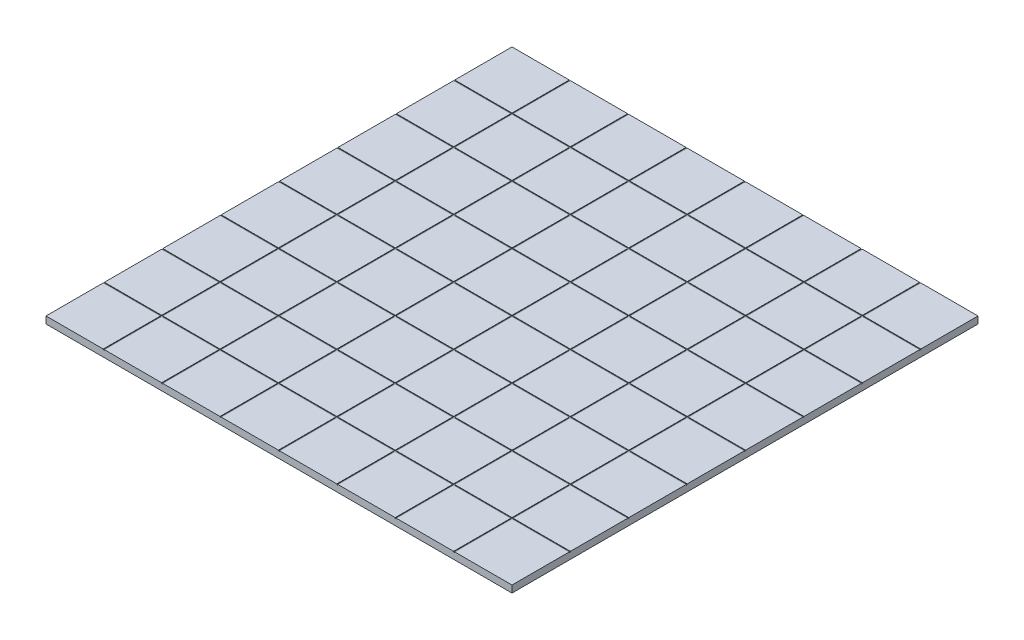
SolidWorks part; units mm, degrees
ref_plane "Front Plane" through (0, 0, 0) normal (0, 0, 1) x (1, 0, 0)
ref_plane "Top Plane" through (0, 0, 0) normal (0, 1, 0) x (1, 0, 0)
ref_plane "Right Plane" through (0, 0, 0) normal (1, 0, 0) x (0, 0, -1)
sketch "Sketch1" plane through (0, 0, 0) normal (0, 1, 0) x (1, 0, 0)
  line L1 (0, 0) -> (200, 0)
  line L2 (0, 0) -> (0, 200)
  line L3 (0, 200) -> (200, 200)
  line L4 (200, 0) -> (200, 200)
  dimension "D1" = 200
  dimension "D2" = 200
extrude "Boss-Extrude1" add sketch "Sketch1" along normal blind 3
sketch "Sketch2" plane through (0, 3, 0) normal (0, 1, 0) x (1, 0, 0)
  line L0 (200, 200) -> (0, 200) construction
  line L1 (24.5625, 200) -> (25.0625, 200)
  line L2 (24.5625, 200) -> (24.5625, 0)
  line L3 (24.5625, 0) -> (25.0625, 0)
  line L4 (25.0625, 200) -> (25.0625, 0)
  line L5 (0, 0) -> (200, 0) construction
  line L6 (200, 0) -> (200, 200) construction
  line L7 (49.625, 0) -> (50.125, 0)
  line L8 (49.625, 0) -> (49.625, 200)
  line L9 (49.625, 200) -> (50.125, 200)
  line L10 (50.125, 0) -> (50.125, 200)
  line L11 (99.75, 0) -> (100.25, 0)
  line L12 (99.75, 0) -> (99.75, 200)
  line L13 (99.75, 200) -> (100.25, 200)
  line L14 (100.25, 0) -> (100.25, 200)
  line L15 (74.6875, 0) -> (75.1875, 0)
  line L16 (74.6875, 0) -> (74.6875, 200)
  line L17 (74.6875, 200) -> (75.1875, 200)
  line L18 (75.1875, 0) -> (75.1875, 200)
  line L19 (124.8125, 0) -> (125.3125, 0)
  line L20 (124.8125, 0) -> (124.8125, 200)
  line L21 (124.8125, 200) -> (125.3125, 200)
  line L22 (125.3125, 0) -> (125.3125, 200)
  line L23 (149.875, 0) -> (150.375, 0)
  line L24 (149.875, 0) -> (149.875, 200)
  line L25 (149.875, 200) -> (150.375, 200)
  line L26 (150.375, 0) -> (150.375, 200)
  line L27 (174.9375, 0) -> (175.4375, 0)
  line L28 (174.9375, 0) -> (174.9375, 200)
  line L29 (174.9375, 200) -> (175.4375, 200)
  line L30 (175.4375, 0) -> (175.4375, 200)
  line L31 (0, 200) -> (0, 0) construction
  line L33 (0, 175.4375) -> (200, 175.4375)
  line L34 (0, 175.4375) -> (0, 174.9375)
  line L35 (0, 174.9375) -> (200, 174.9375)
  line L36 (200, 175.4375) -> (200, 174.9375)
  line L37 (0, 150.375) -> (200, 150.375)
  line L38 (0, 150.375) -> (0, 149.875)
  line L39 (0, 149.875) -> (200, 149.875)
  line L40 (200, 150.375) -> (200, 149.875)
  line L41 (0, 125.3125) -> (200, 125.3125)
  line L42 (0, 125.3125) -> (0, 124.8125)
  line L43 (0, 124.8125) -> (200, 124.8125)
  line L44 (200, 125.3125) -> (200, 124.8125)
  line L45 (0, 100.25) -> (200, 100.25)
  line L46 (0, 100.25) -> (0, 99.75)
  line L47 (0, 99.75) -> (200, 99.75)
  line L48 (200, 100.25) -> (200, 99.75)
  line L49 (0, 75.1875) -> (200, 75.1875)
  line L50 (0, 75.1875) -> (0, 74.6875)
  line L51 (0, 74.6875) -> (200, 74.6875)
  line L52 (200, 75.1875) -> (200, 74.6875)
  line L53 (0, 50.125) -> (200, 50.125)
  line L54 (0, 50.125) -> (0, 49.625)
  line L55 (0, 49.625) -> (200, 49.625)
  line L56 (200, 50.125) -> (200, 49.625)
  line L57 (0, 25.0625) -> (200, 25.0625)
  line L58 (0, 25.0625) -> (0, 24.5625)
  line L59 (0, 24.5625) -> (200, 24.5625)
  line L60 (200, 25.0625) -> (200, 24.5625)
  line M29 (0, 200) -> (0, 0)
  dimension "D1" = 0.5
  dimension "D2" = 0.5
  dimension "D3" = 0.5
  dimension "D4" = 0.5
  dimension "D5" = 0.5
  dimension "D6" = 0.5
  dimension "D7" = 0.5
  dimension "D8" = 24.5625
  dimension "D9" = 0.5
  dimension "D10" = 24.5625
  dimension "D11" = 24.5625
  dimension "D12" = 24.5625
  dimension "D13" = 24.5625
  dimension "D14" = 24.5625
  dimension "D15" = 24.5625
  dimension "D16" = 24.5625
  dimension "D17" = 0.5
  dimension "D18" = 24.5625
  dimension "D19" = 0.5
  dimension "D20" = 24.5625
  dimension "D21" = 0.5
  dimension "D22" = 24.5625
  dimension "D23" = 0.5
  dimension "D24" = 24.5625
  dimension "D25" = 0.5
  dimension "D26" = 24.5625
  dimension "D27" = 0.5
  dimension "D28" = 24.5625
  dimension "D29" = 0.5
  dimension "D30" = 24.5625
  dimension "D31" = 24.5625
extrude "Cut-Extrude1" cut sketch "Sketch2" against normal blind 0.25 contours L51 L2 L49 M29 | L2 L3 L4 L1 | L49 L52 L51 L50 | L57 L60 L59 L58 | L55 L56 L53 L54 | L47 L48 L45 L46 | L41 L44 L43 L42 | L39 L40 L37 L38 | L33 L36 L35 L34 | L8 L9 L10 L7 | L18 L17 L16 L15 | L12 L13 L14 L11 | L20 L21 L22 L19 | L26 L25 L24 L23 | L30 L29 L28 L27 region at (12.2813, 3, -74.9375)
sketch "Sketch4" plane through (0, 0, 0) normal (0, -1, 0) x (1, 0, 0)
  line L0 (12.28, -186.22) -> (12.28, -189.22)
  line L1 (10.33, -186.22) -> (14.23, -186.22)
  line L2 (10.33, -186.22) -> (10.33, -189.22)
  line L3 (10.33, -189.22) -> (14.23, -189.22)
  line L4 (24.5625, -175.4375) -> (0, -175.4375)
  line L5 (24.5625, -200) -> (24.5625, -175.4375)
  line L6 (0, -200) -> (24.5625, -200)
  line L7 (0, -175.4375) -> (0, -200)
  line L8 (24.5625, -175.4375) -> (0, -175.4375)
  line L9 (24.5625, -200) -> (24.5625, -175.4375)
  line L10 (0, -200) -> (24.5625, -200)
  line L11 (0, -175.4375) -> (0, -200)
  line L12 (14.23, -186.22) -> (14.23, -189.22)
  line L13 (10.33, -187.72) -> (14.23, -187.72)
  line L14 (39.5425, -189.47) -> (39.5425, -185.97)
  line L15 (14.48, -189.47) -> (10.08, -189.47)
  line L16 (14.48, -189.47) -> (14.48, -185.97)
  line L17 (14.48, -185.97) -> (10.08, -185.97)
  line L18 (10.08, -189.47) -> (10.08, -185.97)
  line L19 (14.48, -189.47) -> (10.08, -185.97) construction
  line L20 (14.48, -185.97) -> (10.08, -189.47) construction
  line L21 (39.5425, -189.47) -> (35.1425, -189.47)
  line L22 (35.1425, -189.47) -> (35.1425, -185.97)
  line L23 (39.5425, -185.97) -> (35.1425, -185.97)
  line L24 (25.0625, -175.4375) -> (25.0625, -200)
  line L25 (49.625, -175.4375) -> (25.0625, -175.4375)
  line L26 (49.625, -200) -> (49.625, -175.4375)
  line L27 (25.0625, -200) -> (49.625, -200)
  line L28 (25.0625, -175.4375) -> (25.0625, -200)
  line L29 (49.625, -175.4375) -> (25.0625, -175.4375)
  line L30 (49.625, -200) -> (49.625, -175.4375)
  line L31 (25.0625, -200) -> (49.625, -200)
  line L32 (64.605, -189.47) -> (64.605, -185.97)
  line L33 (64.605, -189.47) -> (60.205, -189.47)
  line L34 (60.205, -189.47) -> (60.205, -185.97)
  line L35 (64.605, -185.97) -> (60.205, -185.97)
  line L36 (89.6675, -189.47) -> (89.6675, -185.97)
  line L37 (89.6675, -189.47) -> (85.2675, -189.47)
  line L38 (85.2675, -189.47) -> (85.2675, -185.97)
  line L39 (89.6675, -185.97) -> (85.2675, -185.97)
  line L40 (114.73, -189.47) -> (114.73, -185.97)
  line L41 (114.73, -189.47) -> (110.33, -189.47)
  line L42 (110.33, -189.47) -> (110.33, -185.97)
  line L43 (114.73, -185.97) -> (110.33, -185.97)
  line L44 (139.7925, -189.47) -> (139.7925, -185.97)
  line L45 (139.7925, -189.47) -> (135.3925, -189.47)
  line L46 (135.3925, -189.47) -> (135.3925, -185.97)
  line L47 (139.7925, -185.97) -> (135.3925, -185.97)
  line L48 (164.855, -189.47) -> (164.855, -185.97)
  line L49 (164.855, -189.47) -> (160.455, -189.47)
  line L50 (160.455, -189.47) -> (160.455, -185.97)
  line L51 (164.855, -185.97) -> (160.455, -185.97)
  line L52 (189.9175, -189.47) -> (189.9175, -185.97)
  line L53 (189.9175, -189.47) -> (185.5175, -189.47)
  line L54 (185.5175, -189.47) -> (185.5175, -185.97)
  line L55 (189.9175, -185.97) -> (185.5175, -185.97)
  line L56 (39.5425, -164.4075) -> (39.5425, -160.9075)
  line L57 (39.5425, -164.4075) -> (35.1425, -164.4075)
  line L58 (35.1425, -164.4075) -> (35.1425, -160.9075)
  line L59 (39.5425, -160.9075) -> (35.1425, -160.9075)
  line L60 (64.605, -164.4075) -> (64.605, -160.9075)
  line L61 (64.605, -164.4075) -> (60.205, -164.4075)
  line L62 (60.205, -164.4075) -> (60.205, -160.9075)
  line L63 (64.605, -160.9075) -> (60.205, -160.9075)
  line L64 (89.6675, -164.4075) -> (89.6675, -160.9075)
  line L65 (89.6675, -164.4075) -> (85.2675, -164.4075)
  line L66 (85.2675, -164.4075) -> (85.2675, -160.9075)
  line L67 (89.6675, -160.9075) -> (85.2675, -160.9075)
  line L68 (114.73, -164.4075) -> (114.73, -160.9075)
  line L69 (114.73, -164.4075) -> (110.33, -164.4075)
  line L70 (110.33, -164.4075) -> (110.33, -160.9075)
  line L71 (114.73, -160.9075) -> (110.33, -160.9075)
  line L72 (139.7925, -164.4075) -> (139.7925, -160.9075)
  line L73 (139.7925, -164.4075) -> (135.3925, -164.4075)
  line L74 (135.3925, -164.4075) -> (135.3925, -160.9075)
  line L75 (139.7925, -160.9075) -> (135.3925, -160.9075)
  line L76 (164.855, -164.4075) -> (164.855, -160.9075)
  line L77 (164.855, -164.4075) -> (160.455, -164.4075)
  line L78 (160.455, -164.4075) -> (160.455, -160.9075)
  line L79 (164.855, -160.9075) -> (160.455, -160.9075)
  line L80 (189.9175, -164.4075) -> (189.9175, -160.9075)
  line L81 (189.9175, -164.4075) -> (185.5175, -164.4075)
  line L82 (185.5175, -164.4075) -> (185.5175, -160.9075)
  line L83 (189.9175, -160.9075) -> (185.5175, -160.9075)
  line L84 (39.5425, -139.345) -> (39.5425, -135.845)
  line L85 (39.5425, -139.345) -> (35.1425, -139.345)
  line L86 (35.1425, -139.345) -> (35.1425, -135.845)
  line L87 (39.5425, -135.845) -> (35.1425, -135.845)
  line L88 (64.605, -139.345) -> (64.605, -135.845)
  line L89 (64.605, -139.345) -> (60.205, -139.345)
  line L90 (60.205, -139.345) -> (60.205, -135.845)
  line L91 (64.605, -135.845) -> (60.205, -135.845)
  line L92 (89.6675, -139.345) -> (89.6675, -135.845)
  line L93 (89.6675, -139.345) -> (85.2675, -139.345)
  line L94 (85.2675, -139.345) -> (85.2675, -135.845)
  line L95 (89.6675, -135.845) -> (85.2675, -135.845)
  line L96 (114.73, -139.345) -> (114.73, -135.845)
  line L97 (114.73, -139.345) -> (110.33, -139.345)
  line L98 (110.33, -139.345) -> (110.33, -135.845)
  line L99 (114.73, -135.845) -> (110.33, -135.845)
  line L100 (139.7925, -139.345) -> (139.7925, -135.845)
  line L101 (139.7925, -139.345) -> (135.3925, -139.345)
  line L102 (135.3925, -139.345) -> (135.3925, -135.845)
  line L103 (139.7925, -135.845) -> (135.3925, -135.845)
  line L104 (164.855, -139.345) -> (164.855, -135.845)
  line L105 (164.855, -139.345) -> (160.455, -139.345)
  line L106 (160.455, -139.345) -> (160.455, -135.845)
  line L107 (164.855, -135.845) -> (160.455, -135.845)
  line L108 (189.9175, -139.345) -> (189.9175, -135.845)
  line L109 (189.9175, -139.345) -> (185.5175, -139.345)
  line L110 (185.5175, -139.345) -> (185.5175, -135.845)
  line L111 (189.9175, -135.845) -> (185.5175, -135.845)
  line L112 (39.5425, -114.2825) -> (39.5425, -110.7825)
  line L113 (39.5425, -114.2825) -> (35.1425, -114.2825)
  line L114 (35.1425, -114.2825) -> (35.1425, -110.7825)
  line L115 (39.5425, -110.7825) -> (35.1425, -110.7825)
  line L116 (64.605, -114.2825) -> (64.605, -110.7825)
  line L117 (64.605, -114.2825) -> (60.205, -114.2825)
  line L118 (60.205, -114.2825) -> (60.205, -110.7825)
  line L119 (64.605, -110.7825) -> (60.205, -110.7825)
  line L120 (89.6675, -114.2825) -> (89.6675, -110.7825)
  line L121 (89.6675, -114.2825) -> (85.2675, -114.2825)
  line L122 (85.2675, -114.2825) -> (85.2675, -110.7825)
  line L123 (89.6675, -110.7825) -> (85.2675, -110.7825)
  line L124 (114.73, -114.2825) -> (114.73, -110.7825)
  line L125 (114.73, -114.2825) -> (110.33, -114.2825)
  line L126 (110.33, -114.2825) -> (110.33, -110.7825)
  line L127 (114.73, -110.7825) -> (110.33, -110.7825)
  line L128 (139.7925, -114.2825) -> (139.7925, -110.7825)
  line L129 (139.7925, -114.2825) -> (135.3925, -114.2825)
  line L130 (135.3925, -114.2825) -> (135.3925, -110.7825)
  line L131 (139.7925, -110.7825) -> (135.3925, -110.7825)
  line L132 (164.855, -114.2825) -> (164.855, -110.7825)
  line L133 (164.855, -114.2825) -> (160.455, -114.2825)
  line L134 (160.455, -114.2825) -> (160.455, -110.7825)
  line L135 (164.855, -110.7825) -> (160.455, -110.7825)
  line L136 (189.9175, -114.2825) -> (189.9175, -110.7825)
  line L137 (189.9175, -114.2825) -> (185.5175, -114.2825)
  line L138 (185.5175, -114.2825) -> (185.5175, -110.7825)
  line L139 (189.9175, -110.7825) -> (185.5175, -110.7825)
  line L140 (39.5425, -89.22) -> (39.5425, -85.72)
  line L141 (39.5425, -89.22) -> (35.1425, -89.22)
  line L142 (35.1425, -89.22) -> (35.1425, -85.72)
  line L143 (39.5425, -85.72) -> (35.1425, -85.72)
  line L144 (64.605, -89.22) -> (64.605, -85.72)
  line L145 (64.605, -89.22) -> (60.205, -89.22)
  line L146 (60.205, -89.22) -> (60.205, -85.72)
  line L147 (64.605, -85.72) -> (60.205, -85.72)
  line L148 (89.6675, -89.22) -> (89.6675, -85.72)
  line L149 (89.6675, -89.22) -> (85.2675, -89.22)
  line L150 (85.2675, -89.22) -> (85.2675, -85.72)
  line L151 (89.6675, -85.72) -> (85.2675, -85.72)
  line L152 (114.73, -89.22) -> (114.73, -85.72)
  line L153 (114.73, -89.22) -> (110.33, -89.22)
  line L154 (110.33, -89.22) -> (110.33, -85.72)
  line L155 (114.73, -85.72) -> (110.33, -85.72)
  line L156 (139.7925, -89.22) -> (139.7925, -85.72)
  line L157 (139.7925, -89.22) -> (135.3925, -89.22)
  line L158 (135.3925, -89.22) -> (135.3925, -85.72)
  line L159 (139.7925, -85.72) -> (135.3925, -85.72)
  line L160 (164.855, -89.22) -> (164.855, -85.72)
  line L161 (164.855, -89.22) -> (160.455, -89.22)
  line L162 (160.455, -89.22) -> (160.455, -85.72)
  line L163 (164.855, -85.72) -> (160.455, -85.72)
  line L164 (189.9175, -89.22) -> (189.9175, -85.72)
  line L165 (189.9175, -89.22) -> (185.5175, -89.22)
  line L166 (185.5175, -89.22) -> (185.5175, -85.72)
  line L167 (189.9175, -85.72) -> (185.5175, -85.72)
  line L168 (39.5425, -64.1575) -> (39.5425, -60.6575)
  line L169 (39.5425, -64.1575) -> (35.1425, -64.1575)
  line L170 (35.1425, -64.1575) -> (35.1425, -60.6575)
  line L171 (39.5425, -60.6575) -> (35.1425, -60.6575)
  line L172 (64.605, -64.1575) -> (64.605, -60.6575)
  line L173 (64.605, -64.1575) -> (60.205, -64.1575)
  line L174 (60.205, -64.1575) -> (60.205, -60.6575)
  line L175 (64.605, -60.6575) -> (60.205, -60.6575)
  line L176 (89.6675, -64.1575) -> (89.6675, -60.6575)
  line L177 (89.6675, -64.1575) -> (85.2675, -64.1575)
  line L178 (85.2675, -64.1575) -> (85.2675, -60.6575)
  line L179 (89.6675, -60.6575) -> (85.2675, -60.6575)
  line L180 (114.73, -64.1575) -> (114.73, -60.6575)
  line L181 (114.73, -64.1575) -> (110.33, -64.1575)
  line L182 (110.33, -64.1575) -> (110.33, -60.6575)
  line L183 (114.73, -60.6575) -> (110.33, -60.6575)
  line L184 (139.7925, -64.1575) -> (139.7925, -60.6575)
  line L185 (139.7925, -64.1575) -> (135.3925, -64.1575)
  line L186 (135.3925, -64.1575) -> (135.3925, -60.6575)
  line L187 (139.7925, -60.6575) -> (135.3925, -60.6575)
  line L188 (164.855, -64.1575) -> (164.855, -60.6575)
  line L189 (164.855, -64.1575) -> (160.455, -64.1575)
  line L190 (160.455, -64.1575) -> (160.455, -60.6575)
  line L191 (164.855, -60.6575) -> (160.455, -60.6575)
  line L192 (189.9175, -64.1575) -> (189.9175, -60.6575)
  line L193 (189.9175, -64.1575) -> (185.5175, -64.1575)
  line L194 (185.5175, -64.1575) -> (185.5175, -60.6575)
  line L195 (189.9175, -60.6575) -> (185.5175, -60.6575)
  line L196 (39.5425, -39.095) -> (39.5425, -35.595)
  line L197 (39.5425, -39.095) -> (35.1425, -39.095)
  line L198 (35.1425, -39.095) -> (35.1425, -35.595)
  line L199 (39.5425, -35.595) -> (35.1425, -35.595)
  line L200 (64.605, -39.095) -> (64.605, -35.595)
  line L201 (64.605, -39.095) -> (60.205, -39.095)
  line L202 (60.205, -39.095) -> (60.205, -35.595)
  line L203 (64.605, -35.595) -> (60.205, -35.595)
  line L204 (89.6675, -39.095) -> (89.6675, -35.595)
  line L205 (89.6675, -39.095) -> (85.2675, -39.095)
  line L206 (85.2675, -39.095) -> (85.2675, -35.595)
  line L207 (89.6675, -35.595) -> (85.2675, -35.595)
  line L208 (114.73, -39.095) -> (114.73, -35.595)
  line L209 (114.73, -39.095) -> (110.33, -39.095)
  line L210 (110.33, -39.095) -> (110.33, -35.595)
  line L211 (114.73, -35.595) -> (110.33, -35.595)
  line L212 (139.7925, -39.095) -> (139.7925, -35.595)
  line L213 (139.7925, -39.095) -> (135.3925, -39.095)
  line L214 (135.3925, -39.095) -> (135.3925, -35.595)
  line L215 (139.7925, -35.595) -> (135.3925, -35.595)
  line L216 (164.855, -39.095) -> (164.855, -35.595)
  line L217 (164.855, -39.095) -> (160.455, -39.095)
  line L218 (160.455, -39.095) -> (160.455, -35.595)
  line L219 (164.855, -35.595) -> (160.455, -35.595)
  line L220 (189.9175, -39.095) -> (189.9175, -35.595)
  line L221 (189.9175, -39.095) -> (185.5175, -39.095)
  line L222 (185.5175, -39.095) -> (185.5175, -35.595)
  line L223 (189.9175, -35.595) -> (185.5175, -35.595)
  line L224 (39.5425, -14.0325) -> (39.5425, -10.5325)
  line L225 (39.5425, -14.0325) -> (35.1425, -14.0325)
  line L226 (35.1425, -14.0325) -> (35.1425, -10.5325)
  line L227 (39.5425, -10.5325) -> (35.1425, -10.5325)
  line L228 (64.605, -14.0325) -> (64.605, -10.5325)
  line L229 (64.605, -14.0325) -> (60.205, -14.0325)
  line L230 (60.205, -14.0325) -> (60.205, -10.5325)
  line L231 (64.605, -10.5325) -> (60.205, -10.5325)
  line L232 (89.6675, -14.0325) -> (89.6675, -10.5325)
  line L233 (89.6675, -14.0325) -> (85.2675, -14.0325)
  line L234 (85.2675, -14.0325) -> (85.2675, -10.5325)
  line L235 (89.6675, -10.5325) -> (85.2675, -10.5325)
  line L236 (114.73, -14.0325) -> (114.73, -10.5325)
  line L237 (114.73, -14.0325) -> (110.33, -14.0325)
  line L238 (110.33, -14.0325) -> (110.33, -10.5325)
  line L239 (114.73, -10.5325) -> (110.33, -10.5325)
  line L240 (139.7925, -14.0325) -> (139.7925, -10.5325)
  line L241 (139.7925, -14.0325) -> (135.3925, -14.0325)
  line L242 (135.3925, -14.0325) -> (135.3925, -10.5325)
  line L243 (139.7925, -10.5325) -> (135.3925, -10.5325)
  line L244 (164.855, -14.0325) -> (164.855, -10.5325)
  line L245 (164.855, -14.0325) -> (160.455, -14.0325)
  line L246 (160.455, -14.0325) -> (160.455, -10.5325)
  line L247 (164.855, -10.5325) -> (160.455, -10.5325)
  line L248 (189.9175, -14.0325) -> (189.9175, -10.5325)
  line L249 (189.9175, -14.0325) -> (185.5175, -14.0325)
  line L250 (185.5175, -14.0325) -> (185.5175, -10.5325)
  line L251 (189.9175, -10.5325) -> (185.5175, -10.5325)
  line L252 (14.48, -164.4075) -> (14.48, -160.9075)
  line L253 (14.48, -164.4075) -> (10.08, -164.4075)
  line L254 (10.08, -164.4075) -> (10.08, -160.9075)
  line L255 (14.48, -160.9075) -> (10.08, -160.9075)
  line L256 (14.48, -139.345) -> (14.48, -135.845)
  line L257 (14.48, -139.345) -> (10.08, -139.345)
  line L258 (10.08, -139.345) -> (10.08, -135.845)
  line L259 (14.48, -135.845) -> (10.08, -135.845)
  line L260 (14.48, -114.2825) -> (14.48, -110.7825)
  line L261 (14.48, -114.2825) -> (10.08, -114.2825)
  line L262 (10.08, -114.2825) -> (10.08, -110.7825)
  line L263 (14.48, -110.7825) -> (10.08, -110.7825)
  line L264 (14.48, -89.22) -> (14.48, -85.72)
  line L265 (14.48, -89.22) -> (10.08, -89.22)
  line L266 (10.08, -89.22) -> (10.08, -85.72)
  line L267 (14.48, -85.72) -> (10.08, -85.72)
  line L268 (14.48, -64.1575) -> (14.48, -60.6575)
  line L269 (14.48, -64.1575) -> (10.08, -64.1575)
  line L270 (10.08, -64.1575) -> (10.08, -60.6575)
  line L271 (14.48, -60.6575) -> (10.08, -60.6575)
  line L272 (14.48, -39.095) -> (14.48, -35.595)
  line L273 (14.48, -39.095) -> (10.08, -39.095)
  line L274 (10.08, -39.095) -> (10.08, -35.595)
  line L275 (14.48, -35.595) -> (10.08, -35.595)
  line L276 (14.48, -14.0325) -> (14.48, -10.5325)
  line L277 (14.48, -14.0325) -> (10.08, -14.0325)
  line L278 (10.08, -14.0325) -> (10.08, -10.5325)
  line L279 (14.48, -10.5325) -> (10.08, -10.5325)
  line L280 (0, -200) -> (0, 0) construction
  line L281 (200, -200) -> (0, -200) construction
  line L282 (0, -200) -> (0, 0)
  line L283 (200, -200) -> (0, -200)
  line L288 (200, -24.5625) -> (200, 0)
  line L289 (175.4375, -24.5625) -> (200, -24.5625)
  line L290 (175.4375, 0) -> (175.4375, -24.5625)
  line L291 (200, 0) -> (175.4375, 0)
  line L292 (200, -24.5625) -> (200, 0)
  line L293 (175.4375, -24.5625) -> (200, -24.5625)
  line L294 (175.4375, 0) -> (175.4375, -24.5625)
  line L295 (200, 0) -> (175.4375, 0)
  point P12 (12.28, -187.72)
  point P13 (12.28, -187.72)
  dimension "D2" = 3.9
  dimension "D3" = 3
  dimension "D4" = 10.33
  dimension "D5" = 10.3325
  dimension "D6" = 10.78
  dimension "D7" = 10.7825
  dimension "D8" = 0.25
  dimension "D9" = 0.25
  dimension "D10" = 0
  dimension "D14" = 10.08
  dimension "D15" = 10.53
  dimension "D16" = 10.53
  dimension "D17" = 10.08
  dimension "D18" = 10.08
  dimension "D19" = 10.53
  dimension "D1" = 0
  dimension "D13" = 0
  dimension "D11" = 8
  dimension "D12" = 8
extrude "Cut-Extrude2" cut sketch "Sketch4" against normal blind 1.5 contours L56 L59 L58 L57 | L252 L255 L254 L253 | L18 L15 L16 L17 L1 L12 L3 L2 | L13 L0 L3 L12 | L0 L13 L12 L1 | L2 L13 L0 L1 | L13 L2 L3 L0 | L14 L23 L22 L21 | L32 L35 L34 L33 | L36 L39 L38 L37 | L40 L43 L42 L41 | L44 L47 L46 L45 | L48 L51 L50 L49 | L52 L55 L54 L53 | L80 L83 L82 L81 | L76 L79 L78 L77 | L72 L75 L74 L73 | L68 L71 L70 L69 | L64 L67 L66 L65 | L60 L63 L62 L61 | L256 L259 L258 L257 | L84 L87 L86 L85 | L88 L91 L90 L89 | L92 L95 L94 L93 | L96 L99 L98 L97 | L100 L103 L102 L101 | L104 L107 L106 L105 | L108 L111 L110 L109 | L136 L139 L138 L137 | L132 L135 L134 L133 | L128 L131 L130 L129 | L124 L127 L126 L125 | L120 L123 L122 L121 | L116 L119 L118 L117 | L112 L115 L114 L113 | L260 L263 L262 L261 | L264 L267 L266 L265 | L140 L143 L142 L141 | L144 L147 L146 L145 | L148 L151 L150 L149 | L152 L155 L154 L153 | L156 L159 L158 L157 | L160 L163 L162 L161 | L164 L167 L166 L165 | L192 L195 L194 L193 | L188 L191 L190 L189 | L184 L187 L186 L185 | L180 L183 L182 L181 | L176 L179 L178 L177 | L172 L175 L174 L173 | L168 L171 L170 L169 | L268 L271 L270 L269 | L272 L275 L274 L273 | L196 L199 L198 L197 | L200 L203 L202 L201 | L204 L207 L206 L205 | L208 L211 L210 L209 | L212 L215 L214 L213 | L216 L219 L218 L217 | L220 L223 L222 L221 | L248 L251 L250 L249 | L244 L247 L246 L245 | L240 L243 L242 L241 | L236 L239 L238 L237 | L232 L235 L234 L233 | L228 L231 L230 L229 | L276 L279 L278 L277 | L224 L227 L226 L225 region at (13.255, 0, -186.97) region at (11.305, 0, -186.97) region at (13.255, 0, -188.47) region at (11.305, 0, -188.47) region at (37.3425, 0, -187.72) region at (12.28, 0, -189.4138) region at (62.405, 0, -187.72) region at (87.4675, 0, -187.72) region at (112.53, 0, -187.72) region at (137.5925, 0, -187.72) region at (162.655, 0, -187.72) region at (187.7175, 0, -187.72) region at (37.3425, 0, -162.6575) region at (62.405, 0, -162.6575) region at (87.4675, 0, -162.6575) region at (112.53, 0, -162.6575) region at (137.5925, 0, -162.6575) region at (162.655, 0, -162.6575) region at (187.7175, 0, -162.6575) region at (37.3425, 0, -137.595) region at (62.405, 0, -137.595) region at (87.4675, 0, -137.595) region at (112.53, 0, -137.595) region at (137.5925, 0, -137.595) region at (162.655, 0, -137.595) region at (187.7175, 0, -137.595) region at (37.3425, 0, -112.5325) region at (62.405, 0, -112.5325) region at (87.4675, 0, -112.5325) region at (112.53, 0, -112.5325) region at (137.5925, 0, -112.5325) region at (162.655, 0, -112.5325) region at (187.7175, 0, -112.5325) region at (37.3425, 0, -87.47) region at (62.405, 0, -87.47) region at (87.4675, 0, -87.47) region at (112.53, 0, -87.47) region at (137.5925, 0, -87.47) region at (162.655, 0, -87.47) region at (187.7175, 0, -87.47) region at (37.3425, 0, -62.4075) region at (62.405, 0, -62.4075) region at (87.4675, 0, -62.4075) region at (112.53, 0, -62.4075) region at (137.5925, 0, -62.4075) region at (162.655, 0, -62.4075) region at (187.7175, 0, -62.4075) region at (37.3425, 0, -37.345) region at (62.405, 0, -37.345) region at (87.4675, 0, -37.345) region at (112.53, 0, -37.345) region at (137.5925, 0, -37.345) region at (162.655, 0, -37.345) region at (187.7175, 0, -37.345) region at (37.3425, 0, -12.2825) region at (62.405, 0, -12.2825) region at (87.4675, 0, -12.2825) region at (112.53, 0, -12.2825) region at (137.5925, 0, -12.2825) region at (162.655, 0, -12.2825)
sketch "Sketch7" plane through (0, 1.5, 0) normal (0, -1, 0) x (1, 0, 0)
  line L0 (185.5175, -160.9075) -> (185.5175, -164.4075)
  line L1 (185.5175, -185.97) -> (189.9175, -185.97)
  line L2 (185.5175, -185.97) -> (185.5175, -189.47)
  line L3 (185.5175, -189.47) -> (189.9175, -189.47)
  line L4 (189.9175, -185.97) -> (189.9175, -189.47)
  line L5 (186.0175, -186.47) -> (189.4175, -186.47)
  line L6 (186.0175, -186.47) -> (186.0175, -188.97)
  line L7 (186.0175, -188.97) -> (189.4175, -188.97)
  line L8 (189.4175, -186.47) -> (189.4175, -188.97)
  line L9 (185.5175, -160.9075) -> (189.9175, -160.9075)
  line L10 (189.9175, -160.9075) -> (189.9175, -164.4075)
  line L11 (185.5175, -164.4075) -> (189.9175, -164.4075)
  line L12 (186.0175, -161.4075) -> (186.0175, -163.9075)
  line L13 (186.0175, -161.4075) -> (189.4175, -161.4075)
  line L14 (189.4175, -161.4075) -> (189.4175, -163.9075)
  line L15 (186.0175, -163.9075) -> (189.4175, -163.9075)
  line L16 (185.5175, -135.845) -> (185.5175, -139.345)
  line L17 (185.5175, -135.845) -> (189.9175, -135.845)
  line L18 (189.9175, -135.845) -> (189.9175, -139.345)
  line L19 (185.5175, -139.345) -> (189.9175, -139.345)
  line L20 (186.0175, -136.345) -> (186.0175, -138.845)
  line L21 (186.0175, -136.345) -> (189.4175, -136.345)
  line L22 (189.4175, -136.345) -> (189.4175, -138.845)
  line L23 (186.0175, -138.845) -> (189.4175, -138.845)
  line L24 (185.5175, -110.7825) -> (185.5175, -114.2825)
  line L25 (185.5175, -110.7825) -> (189.9175, -110.7825)
  line L26 (189.9175, -110.7825) -> (189.9175, -114.2825)
  line L27 (185.5175, -114.2825) -> (189.9175, -114.2825)
  line L28 (186.0175, -111.2825) -> (186.0175, -113.7825)
  line L29 (186.0175, -111.2825) -> (189.4175, -111.2825)
  line L30 (189.4175, -111.2825) -> (189.4175, -113.7825)
  line L31 (186.0175, -113.7825) -> (189.4175, -113.7825)
  line L32 (185.5175, -85.72) -> (185.5175, -89.22)
  line L33 (185.5175, -85.72) -> (189.9175, -85.72)
  line L34 (189.9175, -85.72) -> (189.9175, -89.22)
  line L35 (185.5175, -89.22) -> (189.9175, -89.22)
  line L36 (186.0175, -86.22) -> (186.0175, -88.72)
  line L37 (186.0175, -86.22) -> (189.4175, -86.22)
  line L38 (189.4175, -86.22) -> (189.4175, -88.72)
  line L39 (186.0175, -88.72) -> (189.4175, -88.72)
  line L40 (185.5175, -60.6575) -> (185.5175, -64.1575)
  line L41 (185.5175, -60.6575) -> (189.9175, -60.6575)
  line L42 (189.9175, -60.6575) -> (189.9175, -64.1575)
  line L43 (185.5175, -64.1575) -> (189.9175, -64.1575)
  line L44 (186.0175, -61.1575) -> (186.0175, -63.6575)
  line L45 (186.0175, -61.1575) -> (189.4175, -61.1575)
  line L46 (189.4175, -61.1575) -> (189.4175, -63.6575)
  line L47 (186.0175, -63.6575) -> (189.4175, -63.6575)
  line L48 (185.5175, -35.595) -> (185.5175, -39.095)
  line L49 (185.5175, -35.595) -> (189.9175, -35.595)
  line L50 (189.9175, -35.595) -> (189.9175, -39.095)
  line L51 (185.5175, -39.095) -> (189.9175, -39.095)
  line L52 (186.0175, -36.095) -> (186.0175, -38.595)
  line L53 (186.0175, -36.095) -> (189.4175, -36.095)
  line L54 (189.4175, -36.095) -> (189.4175, -38.595)
  line L55 (186.0175, -38.595) -> (189.4175, -38.595)
  line L56 (185.5175, -10.5325) -> (185.5175, -14.0325)
  line L57 (185.5175, -10.5325) -> (189.9175, -10.5325)
  line L58 (189.9175, -10.5325) -> (189.9175, -14.0325)
  line L59 (185.5175, -14.0325) -> (189.9175, -14.0325)
  line L60 (186.0175, -11.0325) -> (186.0175, -13.5325)
  line L61 (186.0175, -11.0325) -> (189.4175, -11.0325)
  line L62 (189.4175, -11.0325) -> (189.4175, -13.5325)
  line L63 (186.0175, -13.5325) -> (189.4175, -13.5325)
  line L64 (160.455, -160.9075) -> (160.455, -164.4075)
  line L65 (160.455, -160.9075) -> (164.855, -160.9075)
  line L66 (164.855, -160.9075) -> (164.855, -164.4075)
  line L67 (160.455, -164.4075) -> (164.855, -164.4075)
  line L68 (160.955, -161.4075) -> (160.955, -163.9075)
  line L69 (160.955, -161.4075) -> (164.355, -161.4075)
  line L70 (164.355, -161.4075) -> (164.355, -163.9075)
  line L71 (160.955, -163.9075) -> (164.355, -163.9075)
  line L72 (160.455, -135.845) -> (160.455, -139.345)
  line L73 (160.455, -135.845) -> (164.855, -135.845)
  line L74 (164.855, -135.845) -> (164.855, -139.345)
  line L75 (160.455, -139.345) -> (164.855, -139.345)
  line L76 (160.955, -136.345) -> (160.955, -138.845)
  line L77 (160.955, -136.345) -> (164.355, -136.345)
  line L78 (164.355, -136.345) -> (164.355, -138.845)
  line L79 (160.955, -138.845) -> (164.355, -138.845)
  line L80 (160.455, -110.7825) -> (160.455, -114.2825)
  line L81 (160.455, -110.7825) -> (164.855, -110.7825)
  line L82 (164.855, -110.7825) -> (164.855, -114.2825)
  line L83 (160.455, -114.2825) -> (164.855, -114.2825)
  line L84 (160.955, -111.2825) -> (160.955, -113.7825)
  line L85 (160.955, -111.2825) -> (164.355, -111.2825)
  line L86 (164.355, -111.2825) -> (164.355, -113.7825)
  line L87 (160.955, -113.7825) -> (164.355, -113.7825)
  line L88 (160.455, -85.72) -> (160.455, -89.22)
  line L89 (160.455, -85.72) -> (164.855, -85.72)
  line L90 (164.855, -85.72) -> (164.855, -89.22)
  line L91 (160.455, -89.22) -> (164.855, -89.22)
  line L92 (160.955, -86.22) -> (160.955, -88.72)
  line L93 (160.955, -86.22) -> (164.355, -86.22)
  line L94 (164.355, -86.22) -> (164.355, -88.72)
  line L95 (160.955, -88.72) -> (164.355, -88.72)
  line L96 (160.455, -60.6575) -> (160.455, -64.1575)
  line L97 (160.455, -60.6575) -> (164.855, -60.6575)
  line L98 (164.855, -60.6575) -> (164.855, -64.1575)
  line L99 (160.455, -64.1575) -> (164.855, -64.1575)
  line L100 (160.955, -61.1575) -> (160.955, -63.6575)
  line L101 (160.955, -61.1575) -> (164.355, -61.1575)
  line L102 (164.355, -61.1575) -> (164.355, -63.6575)
  line L103 (160.955, -63.6575) -> (164.355, -63.6575)
  line L104 (160.455, -35.595) -> (160.455, -39.095)
  line L105 (160.455, -35.595) -> (164.855, -35.595)
  line L106 (164.855, -35.595) -> (164.855, -39.095)
  line L107 (160.455, -39.095) -> (164.855, -39.095)
  line L108 (160.955, -36.095) -> (160.955, -38.595)
  line L109 (160.955, -36.095) -> (164.355, -36.095)
  line L110 (164.355, -36.095) -> (164.355, -38.595)
  line L111 (160.955, -38.595) -> (164.355, -38.595)
  line L112 (160.455, -10.5325) -> (160.455, -14.0325)
  line L113 (160.455, -10.5325) -> (164.855, -10.5325)
  line L114 (164.855, -10.5325) -> (164.855, -14.0325)
  line L115 (160.455, -14.0325) -> (164.855, -14.0325)
  line L116 (160.955, -11.0325) -> (160.955, -13.5325)
  line L117 (160.955, -11.0325) -> (164.355, -11.0325)
  line L118 (164.355, -11.0325) -> (164.355, -13.5325)
  line L119 (160.955, -13.5325) -> (164.355, -13.5325)
  line L120 (135.3925, -160.9075) -> (135.3925, -164.4075)
  line L121 (135.3925, -160.9075) -> (139.7925, -160.9075)
  line L122 (139.7925, -160.9075) -> (139.7925, -164.4075)
  line L123 (135.3925, -164.4075) -> (139.7925, -164.4075)
  line L124 (135.8925, -161.4075) -> (135.8925, -163.9075)
  line L125 (135.8925, -161.4075) -> (139.2925, -161.4075)
  line L126 (139.2925, -161.4075) -> (139.2925, -163.9075)
  line L127 (135.8925, -163.9075) -> (139.2925, -163.9075)
  line L128 (135.3925, -135.845) -> (135.3925, -139.345)
  line L129 (135.3925, -135.845) -> (139.7925, -135.845)
  line L130 (139.7925, -135.845) -> (139.7925, -139.345)
  line L131 (135.3925, -139.345) -> (139.7925, -139.345)
  line L132 (135.8925, -136.345) -> (135.8925, -138.845)
  line L133 (135.8925, -136.345) -> (139.2925, -136.345)
  line L134 (139.2925, -136.345) -> (139.2925, -138.845)
  line L135 (135.8925, -138.845) -> (139.2925, -138.845)
  line L136 (135.3925, -110.7825) -> (135.3925, -114.2825)
  line L137 (135.3925, -110.7825) -> (139.7925, -110.7825)
  line L138 (139.7925, -110.7825) -> (139.7925, -114.2825)
  line L139 (135.3925, -114.2825) -> (139.7925, -114.2825)
  line L140 (135.8925, -111.2825) -> (135.8925, -113.7825)
  line L141 (135.8925, -111.2825) -> (139.2925, -111.2825)
  line L142 (139.2925, -111.2825) -> (139.2925, -113.7825)
  line L143 (135.8925, -113.7825) -> (139.2925, -113.7825)
  line L144 (135.3925, -85.72) -> (135.3925, -89.22)
  line L145 (135.3925, -85.72) -> (139.7925, -85.72)
  line L146 (139.7925, -85.72) -> (139.7925, -89.22)
  line L147 (135.3925, -89.22) -> (139.7925, -89.22)
  line L148 (135.8925, -86.22) -> (135.8925, -88.72)
  line L149 (135.8925, -86.22) -> (139.2925, -86.22)
  line L150 (139.2925, -86.22) -> (139.2925, -88.72)
  line L151 (135.8925, -88.72) -> (139.2925, -88.72)
  line L152 (135.3925, -60.6575) -> (135.3925, -64.1575)
  line L153 (135.3925, -60.6575) -> (139.7925, -60.6575)
  line L154 (139.7925, -60.6575) -> (139.7925, -64.1575)
  line L155 (135.3925, -64.1575) -> (139.7925, -64.1575)
  line L156 (135.8925, -61.1575) -> (135.8925, -63.6575)
  line L157 (135.8925, -61.1575) -> (139.2925, -61.1575)
  line L158 (139.2925, -61.1575) -> (139.2925, -63.6575)
  line L159 (135.8925, -63.6575) -> (139.2925, -63.6575)
  line L160 (135.3925, -35.595) -> (135.3925, -39.095)
  line L161 (135.3925, -35.595) -> (139.7925, -35.595)
  line L162 (139.7925, -35.595) -> (139.7925, -39.095)
  line L163 (135.3925, -39.095) -> (139.7925, -39.095)
  line L164 (135.8925, -36.095) -> (135.8925, -38.595)
  line L165 (135.8925, -36.095) -> (139.2925, -36.095)
  line L166 (139.2925, -36.095) -> (139.2925, -38.595)
  line L167 (135.8925, -38.595) -> (139.2925, -38.595)
  line L168 (135.3925, -10.5325) -> (135.3925, -14.0325)
  line L169 (135.3925, -10.5325) -> (139.7925, -10.5325)
  line L170 (139.7925, -10.5325) -> (139.7925, -14.0325)
  line L171 (135.3925, -14.0325) -> (139.7925, -14.0325)
  line L172 (135.8925, -11.0325) -> (135.8925, -13.5325)
  line L173 (135.8925, -11.0325) -> (139.2925, -11.0325)
  line L174 (139.2925, -11.0325) -> (139.2925, -13.5325)
  line L175 (135.8925, -13.5325) -> (139.2925, -13.5325)
  line L176 (110.33, -160.9075) -> (110.33, -164.4075)
  line L177 (110.33, -160.9075) -> (114.73, -160.9075)
  line L178 (114.73, -160.9075) -> (114.73, -164.4075)
  line L179 (110.33, -164.4075) -> (114.73, -164.4075)
  line L180 (110.83, -161.4075) -> (110.83, -163.9075)
  line L181 (110.83, -161.4075) -> (114.23, -161.4075)
  line L182 (114.23, -161.4075) -> (114.23, -163.9075)
  line L183 (110.83, -163.9075) -> (114.23, -163.9075)
  line L184 (110.33, -135.845) -> (110.33, -139.345)
  line L185 (110.33, -135.845) -> (114.73, -135.845)
  line L186 (114.73, -135.845) -> (114.73, -139.345)
  line L187 (110.33, -139.345) -> (114.73, -139.345)
  line L188 (110.83, -136.345) -> (110.83, -138.845)
  line L189 (110.83, -136.345) -> (114.23, -136.345)
  line L190 (114.23, -136.345) -> (114.23, -138.845)
  line L191 (110.83, -138.845) -> (114.23, -138.845)
  line L192 (110.33, -110.7825) -> (110.33, -114.2825)
  line L193 (110.33, -110.7825) -> (114.73, -110.7825)
  line L194 (114.73, -110.7825) -> (114.73, -114.2825)
  line L195 (110.33, -114.2825) -> (114.73, -114.2825)
  line L196 (110.83, -111.2825) -> (110.83, -113.7825)
  line L197 (110.83, -111.2825) -> (114.23, -111.2825)
  line L198 (114.23, -111.2825) -> (114.23, -113.7825)
  line L199 (110.83, -113.7825) -> (114.23, -113.7825)
  line L200 (110.33, -85.72) -> (110.33, -89.22)
  line L201 (110.33, -85.72) -> (114.73, -85.72)
  line L202 (114.73, -85.72) -> (114.73, -89.22)
  line L203 (110.33, -89.22) -> (114.73, -89.22)
  line L204 (110.83, -86.22) -> (110.83, -88.72)
  line L205 (110.83, -86.22) -> (114.23, -86.22)
  line L206 (114.23, -86.22) -> (114.23, -88.72)
  line L207 (110.83, -88.72) -> (114.23, -88.72)
  line L208 (110.33, -60.6575) -> (110.33, -64.1575)
  line L209 (110.33, -60.6575) -> (114.73, -60.6575)
  line L210 (114.73, -60.6575) -> (114.73, -64.1575)
  line L211 (110.33, -64.1575) -> (114.73, -64.1575)
  line L212 (110.83, -61.1575) -> (110.83, -63.6575)
  line L213 (110.83, -61.1575) -> (114.23, -61.1575)
  line L214 (114.23, -61.1575) -> (114.23, -63.6575)
  line L215 (110.83, -63.6575) -> (114.23, -63.6575)
  line L216 (110.33, -35.595) -> (110.33, -39.095)
  line L217 (110.33, -35.595) -> (114.73, -35.595)
  line L218 (114.73, -35.595) -> (114.73, -39.095)
  line L219 (110.33, -39.095) -> (114.73, -39.095)
  line L220 (110.83, -36.095) -> (110.83, -38.595)
  line L221 (110.83, -36.095) -> (114.23, -36.095)
  line L222 (114.23, -36.095) -> (114.23, -38.595)
  line L223 (110.83, -38.595) -> (114.23, -38.595)
  line L224 (110.33, -10.5325) -> (110.33, -14.0325)
  line L225 (110.33, -10.5325) -> (114.73, -10.5325)
  line L226 (114.73, -10.5325) -> (114.73, -14.0325)
  line L227 (110.33, -14.0325) -> (114.73, -14.0325)
  line L228 (110.83, -11.0325) -> (110.83, -13.5325)
  line L229 (110.83, -11.0325) -> (114.23, -11.0325)
  line L230 (114.23, -11.0325) -> (114.23, -13.5325)
  line L231 (110.83, -13.5325) -> (114.23, -13.5325)
  line L232 (85.2675, -160.9075) -> (85.2675, -164.4075)
  line L233 (85.2675, -160.9075) -> (89.6675, -160.9075)
  line L234 (89.6675, -160.9075) -> (89.6675, -164.4075)
  line L235 (85.2675, -164.4075) -> (89.6675, -164.4075)
  line L236 (85.7675, -161.4075) -> (85.7675, -163.9075)
  line L237 (85.7675, -161.4075) -> (89.1675, -161.4075)
  line L238 (89.1675, -161.4075) -> (89.1675, -163.9075)
  line L239 (85.7675, -163.9075) -> (89.1675, -163.9075)
  line L240 (85.2675, -135.845) -> (85.2675, -139.345)
  line L241 (85.2675, -135.845) -> (89.6675, -135.845)
  line L242 (89.6675, -135.845) -> (89.6675, -139.345)
  line L243 (85.2675, -139.345) -> (89.6675, -139.345)
  line L244 (85.7675, -136.345) -> (85.7675, -138.845)
  line L245 (85.7675, -136.345) -> (89.1675, -136.345)
  line L246 (89.1675, -136.345) -> (89.1675, -138.845)
  line L247 (85.7675, -138.845) -> (89.1675, -138.845)
  line L248 (85.2675, -110.7825) -> (85.2675, -114.2825)
  line L249 (85.2675, -110.7825) -> (89.6675, -110.7825)
  line L250 (89.6675, -110.7825) -> (89.6675, -114.2825)
  line L251 (85.2675, -114.2825) -> (89.6675, -114.2825)
  line L252 (85.7675, -111.2825) -> (85.7675, -113.7825)
  line L253 (85.7675, -111.2825) -> (89.1675, -111.2825)
  line L254 (89.1675, -111.2825) -> (89.1675, -113.7825)
  line L255 (85.7675, -113.7825) -> (89.1675, -113.7825)
  line L256 (85.2675, -85.72) -> (85.2675, -89.22)
  line L257 (85.2675, -85.72) -> (89.6675, -85.72)
  line L258 (89.6675, -85.72) -> (89.6675, -89.22)
  line L259 (85.2675, -89.22) -> (89.6675, -89.22)
  line L260 (85.7675, -86.22) -> (85.7675, -88.72)
  line L261 (85.7675, -86.22) -> (89.1675, -86.22)
  line L262 (89.1675, -86.22) -> (89.1675, -88.72)
  line L263 (85.7675, -88.72) -> (89.1675, -88.72)
  line L264 (85.2675, -60.6575) -> (85.2675, -64.1575)
  line L265 (85.2675, -60.6575) -> (89.6675, -60.6575)
  line L266 (89.6675, -60.6575) -> (89.6675, -64.1575)
  line L267 (85.2675, -64.1575) -> (89.6675, -64.1575)
  line L268 (85.7675, -61.1575) -> (85.7675, -63.6575)
  line L269 (85.7675, -61.1575) -> (89.1675, -61.1575)
  line L270 (89.1675, -61.1575) -> (89.1675, -63.6575)
  line L271 (85.7675, -63.6575) -> (89.1675, -63.6575)
  line L272 (85.2675, -35.595) -> (85.2675, -39.095)
  line L273 (85.2675, -35.595) -> (89.6675, -35.595)
  line L274 (89.6675, -35.595) -> (89.6675, -39.095)
  line L275 (85.2675, -39.095) -> (89.6675, -39.095)
  line L276 (85.7675, -36.095) -> (85.7675, -38.595)
  line L277 (85.7675, -36.095) -> (89.1675, -36.095)
  line L278 (89.1675, -36.095) -> (89.1675, -38.595)
  line L279 (85.7675, -38.595) -> (89.1675, -38.595)
  line L280 (85.2675, -10.5325) -> (85.2675, -14.0325)
  line L281 (85.2675, -10.5325) -> (89.6675, -10.5325)
  line L282 (89.6675, -10.5325) -> (89.6675, -14.0325)
  line L283 (85.2675, -14.0325) -> (89.6675, -14.0325)
  line L284 (85.7675, -11.0325) -> (85.7675, -13.5325)
  line L285 (85.7675, -11.0325) -> (89.1675, -11.0325)
  line L286 (89.1675, -11.0325) -> (89.1675, -13.5325)
  line L287 (85.7675, -13.5325) -> (89.1675, -13.5325)
  line L288 (60.205, -160.9075) -> (60.205, -164.4075)
  line L289 (60.205, -160.9075) -> (64.605, -160.9075)
  line L290 (64.605, -160.9075) -> (64.605, -164.4075)
  line L291 (60.205, -164.4075) -> (64.605, -164.4075)
  line L292 (60.705, -161.4075) -> (60.705, -163.9075)
  line L293 (60.705, -161.4075) -> (64.105, -161.4075)
  line L294 (64.105, -161.4075) -> (64.105, -163.9075)
  line L295 (60.705, -163.9075) -> (64.105, -163.9075)
  line L296 (60.205, -135.845) -> (60.205, -139.345)
  line L297 (60.205, -135.845) -> (64.605, -135.845)
  line L298 (64.605, -135.845) -> (64.605, -139.345)
  line L299 (60.205, -139.345) -> (64.605, -139.345)
  line L300 (60.705, -136.345) -> (60.705, -138.845)
  line L301 (60.705, -136.345) -> (64.105, -136.345)
  line L302 (64.105, -136.345) -> (64.105, -138.845)
  line L303 (60.705, -138.845) -> (64.105, -138.845)
  line L304 (60.205, -110.7825) -> (60.205, -114.2825)
  line L305 (60.205, -110.7825) -> (64.605, -110.7825)
  line L306 (64.605, -110.7825) -> (64.605, -114.2825)
  line L307 (60.205, -114.2825) -> (64.605, -114.2825)
  line L308 (60.705, -111.2825) -> (60.705, -113.7825)
  line L309 (60.705, -111.2825) -> (64.105, -111.2825)
  line L310 (64.105, -111.2825) -> (64.105, -113.7825)
  line L311 (60.705, -113.7825) -> (64.105, -113.7825)
  line L312 (60.205, -85.72) -> (60.205, -89.22)
  line L313 (60.205, -85.72) -> (64.605, -85.72)
  line L314 (64.605, -85.72) -> (64.605, -89.22)
  line L315 (60.205, -89.22) -> (64.605, -89.22)
  line L316 (60.705, -86.22) -> (60.705, -88.72)
  line L317 (60.705, -86.22) -> (64.105, -86.22)
  line L318 (64.105, -86.22) -> (64.105, -88.72)
  line L319 (60.705, -88.72) -> (64.105, -88.72)
  line L320 (60.205, -60.6575) -> (60.205, -64.1575)
  line L321 (60.205, -60.6575) -> (64.605, -60.6575)
  line L322 (64.605, -60.6575) -> (64.605, -64.1575)
  line L323 (60.205, -64.1575) -> (64.605, -64.1575)
  line L324 (60.705, -61.1575) -> (60.705, -63.6575)
  line L325 (60.705, -61.1575) -> (64.105, -61.1575)
  line L326 (64.105, -61.1575) -> (64.105, -63.6575)
  line L327 (60.705, -63.6575) -> (64.105, -63.6575)
  line L328 (60.205, -35.595) -> (60.205, -39.095)
  line L329 (60.205, -35.595) -> (64.605, -35.595)
  line L330 (64.605, -35.595) -> (64.605, -39.095)
  line L331 (60.205, -39.095) -> (64.605, -39.095)
  line L332 (60.705, -36.095) -> (60.705, -38.595)
  line L333 (60.705, -36.095) -> (64.105, -36.095)
  line L334 (64.105, -36.095) -> (64.105, -38.595)
  line L335 (60.705, -38.595) -> (64.105, -38.595)
  line L336 (60.205, -10.5325) -> (60.205, -14.0325)
  line L337 (60.205, -10.5325) -> (64.605, -10.5325)
  line L338 (64.605, -10.5325) -> (64.605, -14.0325)
  line L339 (60.205, -14.0325) -> (64.605, -14.0325)
  line L340 (60.705, -11.0325) -> (60.705, -13.5325)
  line L341 (60.705, -11.0325) -> (64.105, -11.0325)
  line L342 (64.105, -11.0325) -> (64.105, -13.5325)
  line L343 (60.705, -13.5325) -> (64.105, -13.5325)
  line L344 (35.1425, -160.9075) -> (35.1425, -164.4075)
  line L345 (35.1425, -160.9075) -> (39.5425, -160.9075)
  line L346 (39.5425, -160.9075) -> (39.5425, -164.4075)
  line L347 (35.1425, -164.4075) -> (39.5425, -164.4075)
  line L348 (35.6425, -161.4075) -> (35.6425, -163.9075)
  line L349 (35.6425, -161.4075) -> (39.0425, -161.4075)
  line L350 (39.0425, -161.4075) -> (39.0425, -163.9075)
  line L351 (35.6425, -163.9075) -> (39.0425, -163.9075)
  line L352 (35.1425, -135.845) -> (35.1425, -139.345)
  line L353 (35.1425, -135.845) -> (39.5425, -135.845)
  line L354 (39.5425, -135.845) -> (39.5425, -139.345)
  line L355 (35.1425, -139.345) -> (39.5425, -139.345)
  line L356 (35.6425, -136.345) -> (35.6425, -138.845)
  line L357 (35.6425, -136.345) -> (39.0425, -136.345)
  line L358 (39.0425, -136.345) -> (39.0425, -138.845)
  line L359 (35.6425, -138.845) -> (39.0425, -138.845)
  line L360 (35.1425, -110.7825) -> (35.1425, -114.2825)
  line L361 (35.1425, -110.7825) -> (39.5425, -110.7825)
  line L362 (39.5425, -110.7825) -> (39.5425, -114.2825)
  line L363 (35.1425, -114.2825) -> (39.5425, -114.2825)
  line L364 (35.6425, -111.2825) -> (35.6425, -113.7825)
  line L365 (35.6425, -111.2825) -> (39.0425, -111.2825)
  line L366 (39.0425, -111.2825) -> (39.0425, -113.7825)
  line L367 (35.6425, -113.7825) -> (39.0425, -113.7825)
  line L368 (35.1425, -85.72) -> (35.1425, -89.22)
  line L369 (35.1425, -85.72) -> (39.5425, -85.72)
  line L370 (39.5425, -85.72) -> (39.5425, -89.22)
  line L371 (35.1425, -89.22) -> (39.5425, -89.22)
  line L372 (35.6425, -86.22) -> (35.6425, -88.72)
  line L373 (35.6425, -86.22) -> (39.0425, -86.22)
  line L374 (39.0425, -86.22) -> (39.0425, -88.72)
  line L375 (35.6425, -88.72) -> (39.0425, -88.72)
  line L376 (35.1425, -60.6575) -> (35.1425, -64.1575)
  line L377 (35.1425, -60.6575) -> (39.5425, -60.6575)
  line L378 (39.5425, -60.6575) -> (39.5425, -64.1575)
  line L379 (35.1425, -64.1575) -> (39.5425, -64.1575)
  line L380 (35.6425, -61.1575) -> (35.6425, -63.6575)
  line L381 (35.6425, -61.1575) -> (39.0425, -61.1575)
  line L382 (39.0425, -61.1575) -> (39.0425, -63.6575)
  line L383 (35.6425, -63.6575) -> (39.0425, -63.6575)
  line L384 (35.1425, -35.595) -> (35.1425, -39.095)
  line L385 (35.1425, -35.595) -> (39.5425, -35.595)
  line L386 (39.5425, -35.595) -> (39.5425, -39.095)
  line L387 (35.1425, -39.095) -> (39.5425, -39.095)
  line L388 (35.6425, -36.095) -> (35.6425, -38.595)
  line L389 (35.6425, -36.095) -> (39.0425, -36.095)
  line L390 (39.0425, -36.095) -> (39.0425, -38.595)
  line L391 (35.6425, -38.595) -> (39.0425, -38.595)
  line L392 (35.1425, -10.5325) -> (35.1425, -14.0325)
  line L393 (35.1425, -10.5325) -> (39.5425, -10.5325)
  line L394 (39.5425, -10.5325) -> (39.5425, -14.0325)
  line L395 (35.1425, -14.0325) -> (39.5425, -14.0325)
  line L396 (35.6425, -11.0325) -> (35.6425, -13.5325)
  line L397 (35.6425, -11.0325) -> (39.0425, -11.0325)
  line L398 (39.0425, -11.0325) -> (39.0425, -13.5325)
  line L399 (35.6425, -13.5325) -> (39.0425, -13.5325)
  line L400 (10.08, -160.9075) -> (10.08, -164.4075)
  line L401 (10.08, -160.9075) -> (14.48, -160.9075)
  line L402 (14.48, -160.9075) -> (14.48, -164.4075)
  line L403 (10.08, -164.4075) -> (14.48, -164.4075)
  line L404 (10.58, -161.4075) -> (10.58, -163.9075)
  line L405 (10.58, -161.4075) -> (13.98, -161.4075)
  line L406 (13.98, -161.4075) -> (13.98, -163.9075)
  line L407 (10.58, -163.9075) -> (13.98, -163.9075)
  line L408 (10.08, -135.845) -> (10.08, -139.345)
  line L409 (10.08, -135.845) -> (14.48, -135.845)
  line L410 (14.48, -135.845) -> (14.48, -139.345)
  line L411 (10.08, -139.345) -> (14.48, -139.345)
  line L412 (10.58, -136.345) -> (10.58, -138.845)
  line L413 (10.58, -136.345) -> (13.98, -136.345)
  line L414 (13.98, -136.345) -> (13.98, -138.845)
  line L415 (10.58, -138.845) -> (13.98, -138.845)
  line L416 (10.08, -110.7825) -> (10.08, -114.2825)
  line L417 (10.08, -110.7825) -> (14.48, -110.7825)
  line L418 (14.48, -110.7825) -> (14.48, -114.2825)
  line L419 (10.08, -114.2825) -> (14.48, -114.2825)
  line L420 (10.58, -111.2825) -> (10.58, -113.7825)
  line L421 (10.58, -111.2825) -> (13.98, -111.2825)
  line L422 (13.98, -111.2825) -> (13.98, -113.7825)
  line L423 (10.58, -113.7825) -> (13.98, -113.7825)
  line L424 (10.08, -85.72) -> (10.08, -89.22)
  line L425 (10.08, -85.72) -> (14.48, -85.72)
  line L426 (14.48, -85.72) -> (14.48, -89.22)
  line L427 (10.08, -89.22) -> (14.48, -89.22)
  line L428 (10.58, -86.22) -> (10.58, -88.72)
  line L429 (10.58, -86.22) -> (13.98, -86.22)
  line L430 (13.98, -86.22) -> (13.98, -88.72)
  line L431 (10.58, -88.72) -> (13.98, -88.72)
  line L432 (10.08, -60.6575) -> (10.08, -64.1575)
  line L433 (10.08, -60.6575) -> (14.48, -60.6575)
  line L434 (14.48, -60.6575) -> (14.48, -64.1575)
  line L435 (10.08, -64.1575) -> (14.48, -64.1575)
  line L436 (10.58, -61.1575) -> (10.58, -63.6575)
  line L437 (10.58, -61.1575) -> (13.98, -61.1575)
  line L438 (13.98, -61.1575) -> (13.98, -63.6575)
  line L439 (10.58, -63.6575) -> (13.98, -63.6575)
  line L440 (10.08, -35.595) -> (10.08, -39.095)
  line L441 (10.08, -35.595) -> (14.48, -35.595)
  line L442 (14.48, -35.595) -> (14.48, -39.095)
  line L443 (10.08, -39.095) -> (14.48, -39.095)
  line L444 (10.58, -36.095) -> (10.58, -38.595)
  line L445 (10.58, -36.095) -> (13.98, -36.095)
  line L446 (13.98, -36.095) -> (13.98, -38.595)
  line L447 (10.58, -38.595) -> (13.98, -38.595)
  line L448 (10.08, -10.5325) -> (10.08, -14.0325)
  line L449 (10.08, -10.5325) -> (14.48, -10.5325)
  line L450 (14.48, -10.5325) -> (14.48, -14.0325)
  line L451 (10.08, -14.0325) -> (14.48, -14.0325)
  line L452 (10.58, -11.0325) -> (10.58, -13.5325)
  line L453 (10.58, -11.0325) -> (13.98, -11.0325)
  line L454 (13.98, -11.0325) -> (13.98, -13.5325)
  line L455 (10.58, -13.5325) -> (13.98, -13.5325)
  line L456 (160.455, -185.97) -> (160.455, -189.47)
  line L457 (160.455, -185.97) -> (164.855, -185.97)
  line L458 (164.855, -185.97) -> (164.855, -189.47)
  line L459 (160.455, -189.47) -> (164.855, -189.47)
  line L460 (160.955, -186.47) -> (160.955, -188.97)
  line L461 (160.955, -186.47) -> (164.355, -186.47)
  line L462 (164.355, -186.47) -> (164.355, -188.97)
  line L463 (160.955, -188.97) -> (164.355, -188.97)
  line L464 (135.3925, -185.97) -> (135.3925, -189.47)
  line L465 (135.3925, -185.97) -> (139.7925, -185.97)
  line L466 (139.7925, -185.97) -> (139.7925, -189.47)
  line L467 (135.3925, -189.47) -> (139.7925, -189.47)
  line L468 (135.8925, -186.47) -> (135.8925, -188.97)
  line L469 (135.8925, -186.47) -> (139.2925, -186.47)
  line L470 (139.2925, -186.47) -> (139.2925, -188.97)
  line L471 (135.8925, -188.97) -> (139.2925, -188.97)
  line L472 (110.33, -185.97) -> (110.33, -189.47)
  line L473 (110.33, -185.97) -> (114.73, -185.97)
  line L474 (114.73, -185.97) -> (114.73, -189.47)
  line L475 (110.33, -189.47) -> (114.73, -189.47)
  line L476 (110.83, -186.47) -> (110.83, -188.97)
  line L477 (110.83, -186.47) -> (114.23, -186.47)
  line L478 (114.23, -186.47) -> (114.23, -188.97)
  line L479 (110.83, -188.97) -> (114.23, -188.97)
  line L480 (85.2675, -185.97) -> (85.2675, -189.47)
  line L481 (85.2675, -185.97) -> (89.6675, -185.97)
  line L482 (89.6675, -185.97) -> (89.6675, -189.47)
  line L483 (85.2675, -189.47) -> (89.6675, -189.47)
  line L484 (85.7675, -186.47) -> (85.7675, -188.97)
  line L485 (85.7675, -186.47) -> (89.1675, -186.47)
  line L486 (89.1675, -186.47) -> (89.1675, -188.97)
  line L487 (85.7675, -188.97) -> (89.1675, -188.97)
  line L488 (60.205, -185.97) -> (60.205, -189.47)
  line L489 (60.205, -185.97) -> (64.605, -185.97)
  line L490 (64.605, -185.97) -> (64.605, -189.47)
  line L491 (60.205, -189.47) -> (64.605, -189.47)
  line L492 (60.705, -186.47) -> (60.705, -188.97)
  line L493 (60.705, -186.47) -> (64.105, -186.47)
  line L494 (64.105, -186.47) -> (64.105, -188.97)
  line L495 (60.705, -188.97) -> (64.105, -188.97)
  line L496 (35.1425, -185.97) -> (35.1425, -189.47)
  line L497 (35.1425, -185.97) -> (39.5425, -185.97)
  line L498 (39.5425, -185.97) -> (39.5425, -189.47)
  line L499 (35.1425, -189.47) -> (39.5425, -189.47)
  line L500 (35.6425, -186.47) -> (35.6425, -188.97)
  line L501 (35.6425, -186.47) -> (39.0425, -186.47)
  line L502 (39.0425, -186.47) -> (39.0425, -188.97)
  line L503 (35.6425, -188.97) -> (39.0425, -188.97)
  line L504 (10.08, -185.97) -> (10.08, -189.47)
  line L505 (10.08, -185.97) -> (14.48, -185.97)
  line L506 (14.48, -185.97) -> (14.48, -189.47)
  line L507 (10.08, -189.47) -> (14.48, -189.47)
  line L508 (10.58, -186.47) -> (10.58, -188.97)
  line L509 (10.58, -186.47) -> (13.98, -186.47)
  line L510 (13.98, -186.47) -> (13.98, -188.97)
  line L511 (10.58, -188.97) -> (13.98, -188.97)
  dimension "D1" = 0.5
  dimension "D2" = 0.5
  dimension "D3" = 0.5
  dimension "D4" = 0.5
  dimension "D5" = 8
  dimension "D6" = 8
extrude "Cut-Extrude4" cut sketch "Sketch7" against normal up to surface (1.25 mm away) up to face at (100, 2.75, -100)
sketch "Sketch8" plane through (0, 0, 0) normal (0, -1, 0) x (1, 0, 0)
  line L0 (14.48, -14.0325) -> (14.48, -10.5325) construction
  line L1 (14.28, -16.0325) -> (10.28, -16.0325)
  line L2 (14.28, -16.0325) -> (14.28, -19.2725)
  line L3 (14.28, -19.2725) -> (10.28, -19.2725)
  line L4 (10.28, -16.0325) -> (10.28, -19.2725)
  line L5 (10.08, -14.0325) -> (10.08, -10.5325) construction
  line L6 (14.48, -14.0325) -> (10.08, -14.0325) construction
  line L8 (10.03, -15.7825) -> (14.53, -15.7825)
  line L9 (10.03, -15.7825) -> (10.03, -19.5225)
  line L10 (10.03, -19.5225) -> (14.53, -19.5225)
  line L11 (14.53, -15.7825) -> (14.53, -19.5225)
  dimension "D1" = 4
  dimension "D2" = 3.24
  dimension "D3" = 0.2
  dimension "D4" = 0.2
  dimension "D5" = 2
  dimension "D6" = 0.25
  dimension "D7" = 0.25
  dimension "D8" = 0.25
  dimension "D9" = 0.25
extrude "Cut-Extrude5" cut sketch "Sketch8" against normal up to surface (2.75 mm away) contours L1 L4 L3 L2 | L11 L8 L9 L10 L4 L1 L2 L3 region at (12.28, 0, -17.6525) region at (12.28, 0, -15.841) up to face at (12.28, 2.75, -12.2825)
